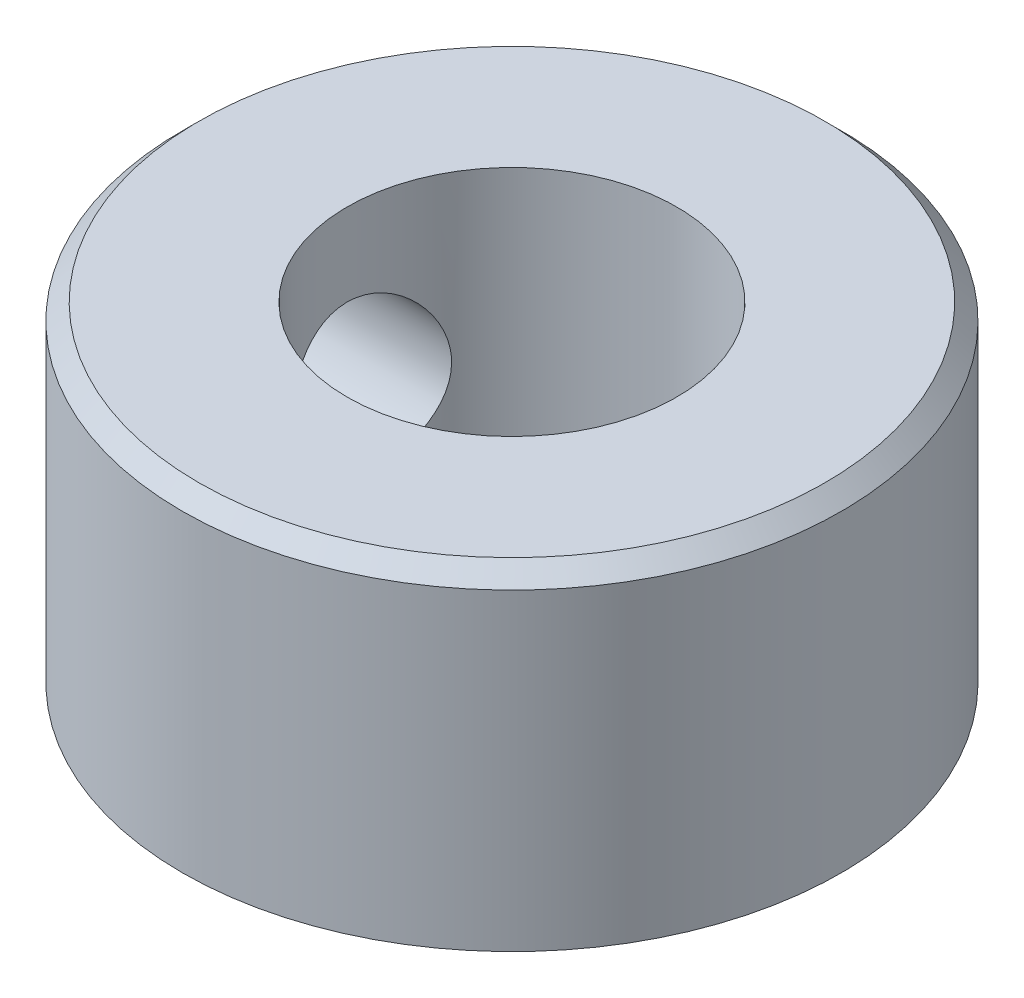
SolidWorks part; units mm, degrees
ref_plane "Front Plane" through (0, 0, 0) normal (0, 0, 1) x (1, 0, 0)
ref_plane "Top Plane" through (0, 0, 0) normal (0, 1, 0) x (1, 0, 0)
ref_plane "Right Plane" through (0, 0, 0) normal (1, 0, 0) x (0, 0, -1)
sketch "Sketch1" plane through (0, 0, 0) normal (0, 1, 0) x (1, 0, 0)
  circle A0 centre (0, 0) radius 10
  circle A1 centre (0, 0) radius 5
  dimension "D1" = 20
  dimension "D2" = 10
extrude "Boss-Extrude1" add sketch "Sketch1" along normal blind 10
ref_axis "Axis1" through (0, 10, 0) along (0, -1, 0)
chamfer "Chamfer1" distance 0.5 angle 45 1 edges at (0, 10, 10)
ref_plane "Plane1" through (0, 5, 0) normal (0, 1, 0) x (1, 0, 0)
ref_plane "Plane2" through (-5, 0, 0) normal (1, 0, 0) x (0, 0, -1)
sketch "Sketch19" plane through (0, 0, 0) normal (1, 0, 0) x (0, 0, -1)
  line L0 (5, 10) -> (-5, 10) construction
  line L2 (0, 5) -> (0, 10) construction
  line L3 (9.5, 10) -> (-9.5, 10) construction
  circle A0 centre (0, 5) radius 2.5
  dimension "D1" = 5
extrude "Cut-Extrude1" cut sketch "Sketch19" against normal up to next
ref_axis "Axis3" through (-10, 5, 0) along (1, 0, 0)
